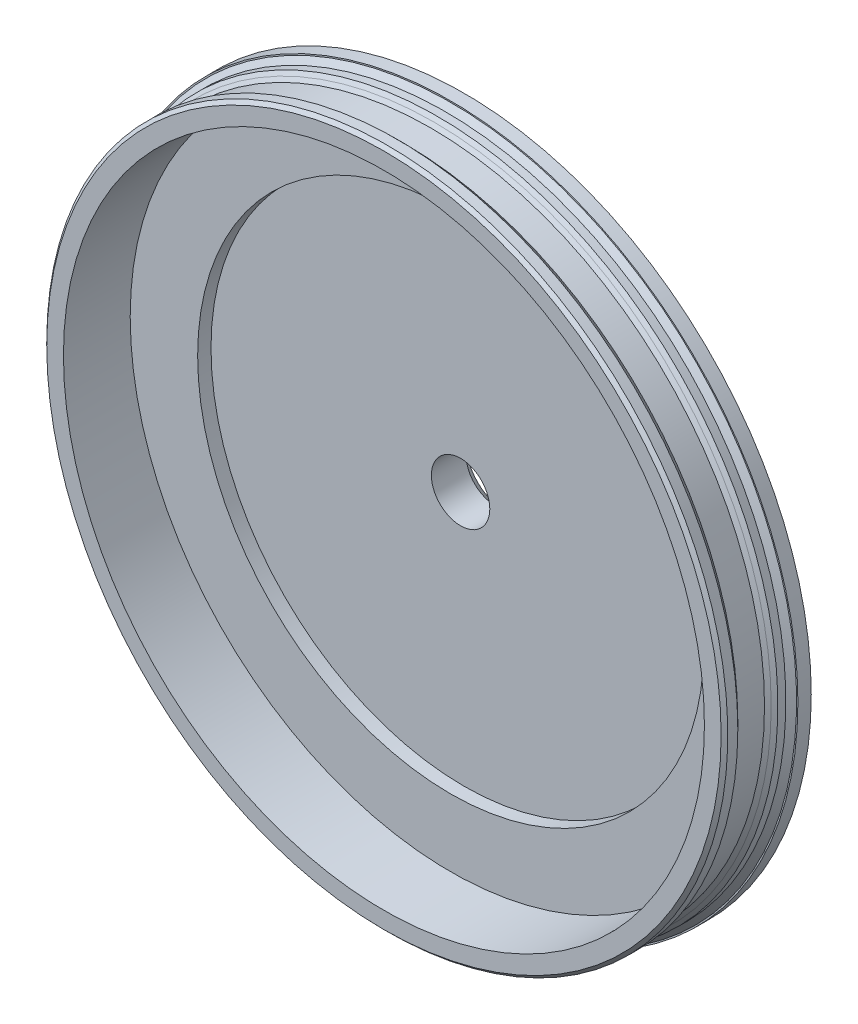
SolidWorks part; units mm, degrees
ref_plane "Front Plane" through (0, 0, 0) normal (0, 0, 1) x (1, 0, 0)
ref_plane "Top Plane" through (0, 0, 0) normal (0, 1, 0) x (1, 0, 0)
ref_plane "Right Plane" through (0, 0, 0) normal (1, 0, 0) x (0, 0, -1)
sketch "Sketch1" plane through (0, 0, 0) normal (0, 1, 0) x (1, 0, 0)
  line L0 (0, 73.9814) -> (0, -55.3241) construction
  line L1 (-91.4726, 0) -> (90.4361, 0) construction
  line L2 (37.9, 0) -> (37.9, -8.7)
  line L3 (48, -18.7) -> (51, -18.7)
  line L4 (51, -18.7) -> (51, -16.2)
  line L5 (51, -16.2) -> (50, -16.2)
  line L6 (50, -16.2) -> (50, -11.2)
  line L7 (50, -11.2) -> (51, -11.2)
  line L8 (51, -11.2) -> (51, -8.7)
  line L9 (51, -8.7) -> (52, -8.7)
  line L10 (52, -8.7) -> (52, -6.7)
  line L11 (52, -6.7) -> (39.9, -6.7)
  line L12 (39.9, -6.7) -> (39.9, 0)
  line L13 (39.9, 0) -> (37.9, 0)
  line L14 (37.9, -8.7) -> (48, -8.7)
  line L15 (48, -8.7) -> (48, -18.7)
  dimension "D1" = 52
  dimension "D2" = 39.9
  dimension "D3" = 51
  dimension "D4" = 6.7
  dimension "D5" = 2
  dimension "D6" = 2
  dimension "D7" = 10
  dimension "D8" = 5
  dimension "D9" = 2.5
  dimension "D10" = 1
  dimension "D11" = 51
  dimension "D12" = 3
revolve "Revolve1" add sketch "Sketch1" angle 360 about L0
chamfer "Chamfer1" distance 0.5 angle 45 6 edges at (-51, 0, 11.2) (-50, 0, 11.2) (-50, 0, 16.2) (-51, 0, 16.2) (-39.9, 0, 0) (-51, 0, 18.7)
sketch "Sketch2" plane through (0, 0, 8.7) normal (0, 0, 1) x (1, 0, 0)
  line L0 (0, 99.1772) -> (0, -96.216) construction
  line L1 (-93.7434, 0) -> (96.5768, 0) construction
  line L2 (-78.2888, 55.25) -> (80.948, 55.25) construction
  line L3 (9.798, 59.25) -> (33.218, 59.25)
  line L4 (-9.798, 59.25) -> (-33.218, 59.25)
  line L12 (46.413, -38.1103) -> (34.703, -58.3926)
  line L13 (56.211, -21.1397) -> (67.921, -0.8574)
  line L14 (85.89, -49.5886) -> (-83.3255, 48.108) construction
  line L15 (86.9923, 40.1751) -> (7.3739, -97.7281) construction
  line L16 (-56.211, -21.1397) -> (-67.921, -0.8574)
  line L17 (-46.413, -38.1103) -> (-34.703, -58.3926)
  line L18 (-85.89, -49.5886) -> (83.3255, 48.108) construction
  line L19 (-8.7035, -95.4251) -> (-88.3219, 42.4781) construction
  line L20 (-33.218, 59.25) -> (-67.921, -0.8574)
  line L21 (-34.703, -58.3926) -> (34.703, -58.3926)
  line L22 (67.921, -0.8574) -> (33.218, 59.25)
  arc A0 (-9.798, 59.25) -> (9.798, 59.25) centre (0, 69.25) ccw
  arc A3 (56.211, -21.1397) -> (46.413, -38.1103) centre (59.9723, -34.625) ccw
  circle A5 centre (0, 0) radius 51 construction
  circle A6 centre (0, 0) radius 51
  arc A7 (-46.413, -38.1103) -> (-56.211, -21.1397) centre (-59.9723, -34.625) ccw
  point P25 (0, 0)
  point P37 (0, 0)
  dimension "D2" = 28
  dimension "D5" = 3
  dimension "D1" = 55.25
  dimension "D3" = 4
  dimension "D4" = 23.42
chamfer "Chamfer2" distance 0.8 angle 45 1 edges at (-51, 0, 8.7)
sketch "Sketch3" plane through (0, 0, 6.7) normal (0, 0, -1) x (-1, 0, 0)
  line L0 (91.4726, 0) -> (-90.4361, 0) construction
  circle A0 centre (0.5183, 0) radius 40.4183
  circle A1 centre (0.5183, 0) radius 4.375
  dimension "D1" = 80.8365
  dimension "D2" = 8.75
extrude "Boss-Extrude1" add sketch "Sketch3" along normal up to surface (6.7 mm away) up to face at (39.4, 0, 0)
chamfer "Chamfer3" distance 1.5 angle 45 1 edges at (3.8567, 0, 0)
